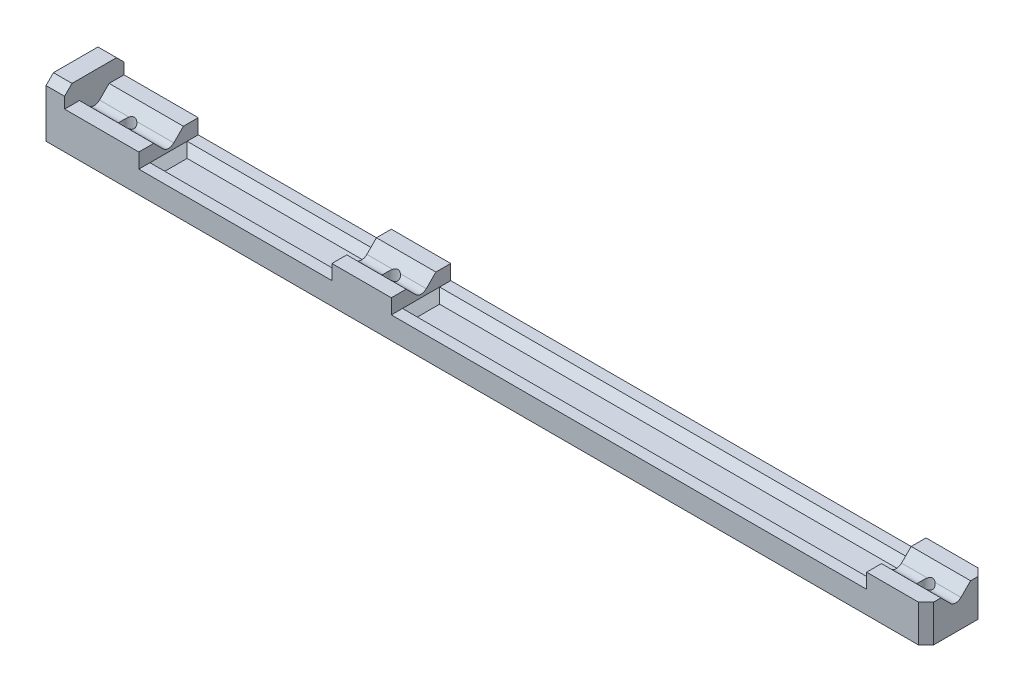
SolidWorks part; units mm, degrees
ref_plane "Спереди" through (0, 0, 0) normal (0, 0, 1) x (1, 0, 0)
ref_plane "Сверху" through (0, 0, 0) normal (0, 1, 0) x (1, 0, 0)
ref_plane "Справа" through (0, 0, 0) normal (1, 0, 0) x (0, 0, -1)
sketch "Эскиз1" plane through (0, 0, 0) normal (1, 0, 0) x (0, 0, -1)
  line L0 (-8, 0) -> (8, 0)
  line L1 (8, 0) -> (8, 10)
  line L2 (4, 10) -> (0, 6)
  line L3 (0, -252.8344) -> (0, 12388.8876) construction
  line L4 (-4, 10) -> (0, 6)
  line L5 (-8, 0) -> (-8, 10)
  line L6 (4, 10) -> (8, 10)
  line L7 (-4, 10) -> (-8, 10)
  circle A0 centre (0, 11.6569) radius 4 construction
  point P0 (4.9867, 9.3539)
  point P7 (0, 0)
  dimension "D1" = 8
  dimension "D2" = 90
  dimension "D3" = 6
  dimension "D4" = 4
  dimension "D5" = 8
extrude "Бобышка-Вытянуть1" add sketch "Эскиз1" along normal blind 20
sketch "Эскиз2" plane through (0, 0, 0) normal (-1, 0, 0) x (0, 0, 1)
  line L0 (8, 10) -> (8, 0) construction
  line L1 (-8, 0) -> (8, 0)
  line L2 (-8, 0) -> (-8, 15)
  line L3 (-8, 15) -> (8, 15)
  line L4 (8, 0) -> (8, 15)
  line L5 (4, 10) -> (8, 10) construction
  point P5 (0, 0)
  dimension "D1" = 5
extrude "Бобышка-Вытянуть2" add sketch "Эскиз2" along normal blind 5
sketch "Эскиз3" plane through (20, 0, 0) normal (1, 0, 0) x (0, 0, -1)
  line L0 (0, -1000) -> (0, 49000) construction
  line L1 (-8, 0) -> (8, 0)
  line L2 (-8, 0) -> (-8, 4)
  line L3 (-5, 4) -> (5, 4)
  line L4 (8, 0) -> (8, 4)
  line L5 (-8, 4) -> (-5, 4) construction
  line L6 (-8, 4) -> (-8, 6)
  line L7 (-8, 6) -> (-5, 6)
  line L8 (-5, 4) -> (-5, 6)
  line L9 (5, 4) -> (5, 6)
  line L10 (8, 6) -> (5, 6)
  line L11 (8, 4) -> (8, 6)
  line L12 (8, 4) -> (5, 4) construction
  line L13 (-8, 4) -> (-5, 4) construction
  line L14 (5, 4) -> (8, 4) construction
  dimension "D1" = 4
  dimension "D2" = 10
  dimension "D3" = 2
extrude "Бобышка-Вытянуть3" add sketch "Эскиз3" along normal up to surface (210 mm away)
ref_plane "Плоскость1" through (80, 0, 0) normal (1, 0, 0) x (0, 0, -1)
sketch "Эскиз4" plane through (80, 0, 0) normal (1, 0, 0) x (0, 0, -1)
  line L7 (-8, 0) -> (8, 0)
  line L8 (8, 0) -> (8, 10)
  line L9 (8, 10) -> (4, 10)
  line L10 (4, 10) -> (0, 6)
  line L11 (0, 6) -> (-4, 10)
  line L12 (-4, 10) -> (-8, 10)
  line L13 (-8, 10) -> (-8, 0)
  line L14 (-8, 0) -> (8, 0)
  line L15 (8, 0) -> (8, 10)
  line L16 (8, 10) -> (4, 10)
  line L17 (4, 10) -> (0, 6)
  line L18 (0, 6) -> (-4, 10)
  line L19 (-4, 10) -> (-8, 10)
  line L20 (-8, 10) -> (-8, 0)
  dimension "D1" = 0
extrude "Бобышка-Вытянуть4" add sketch "Эскиз4" along normal mid plane 16
pattern_linear "Линейный массив1" count 2 spacing 144 along (1, 0, 0) of "Бобышка-Вытянуть4"
fillet "Скругление1" radius 2 3 edges at (224, 6, 0) (80, 6, 0) (10, 6, 0)
chamfer "Фаска1" distance 2 angle 45 12 edges at (232, 5, -8) (232, 5, 8) (216, 4, 0) (152, 4, -5) (88, 4, 0) (152, 4, 5) (20, 4, 0) (46, 4, 5) (72, 4, 0) (46, 4, -5) (-2.5, 15, -8) (-2.5, 15, 8)
sketch "Эскиз5" plane through (0, 0, 0) normal (0, -1, 0) x (1, 0, 0)
  circle A0 centre (9, 0) radius 1.75
  circle A1 centre (9, 0) radius 1
  circle A2 centre (9, 0) radius 1 construction
  circle A3 centre (80, 0) radius 1
  circle A4 centre (80, 0) radius 1 construction
  circle A5 centre (224, 0) radius 1
  circle A6 centre (224, 0) radius 1 construction
  circle A7 centre (80, 0) radius 1.75
  circle A8 centre (224, 0) radius 1.75
  dimension "D4" = 3.5
  dimension "D1" = 0
  dimension "D2" = 0
  dimension "D3" = 0
extrude "Вырез-Вытянуть1" cut sketch "Эскиз5" against normal through all both and the other way through all
